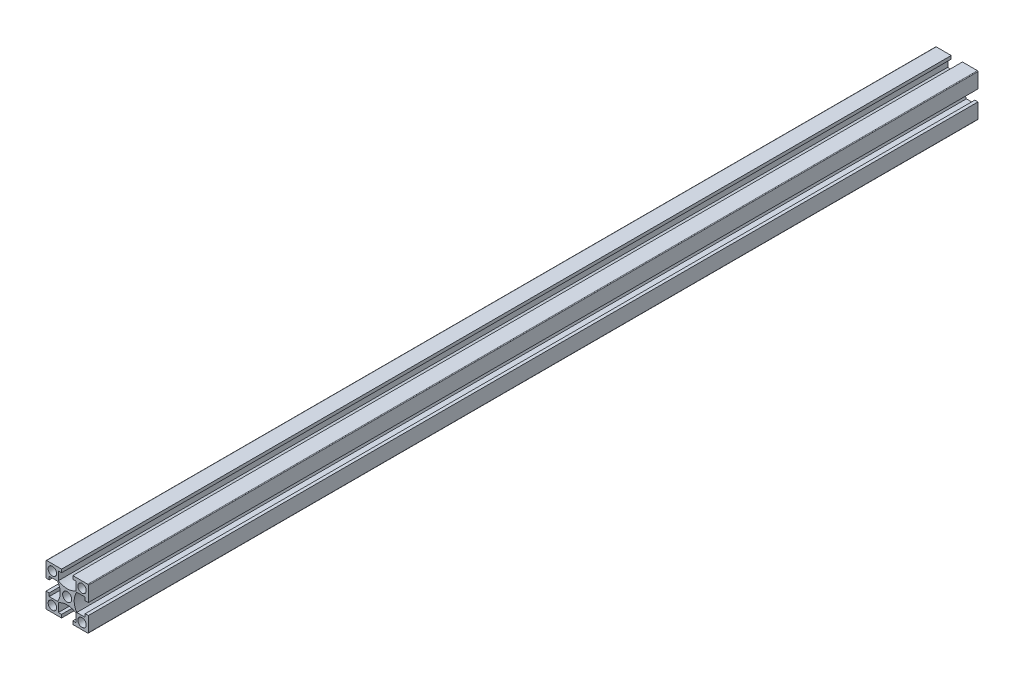
SolidWorks part; units mm, degrees
material "3.0255 (EN-AW 1350A)"
ref_plane "정면" through (0, 0, 0) normal (0, 0, 1) x (1, 0, 0)
ref_plane "윗면" through (0, 0, 0) normal (0, 1, 0) x (1, 0, 0)
ref_plane "우측면" through (0, 0, 0) normal (1, 0, 0) x (0, 0, -1)
sketch "스케치1" plane through (0, 0, 0) normal (0, 0, 1) x (1, 0, 0)
  line L0 (0, 32.0265) -> (0, -31.6588) construction
  line L1 (-10, 10) -> (-10, -10)
  line L2 (-10, 10) -> (10, 10)
  line L3 (-10, 2.65) -> (-8.5, 2.65)
  line L4 (13.6618, 0) -> (-11.6993, 0) construction
  line L5 (-8.5, 2.65) -> (-8.5, 4.15)
  line L6 (-8.5, 4.15) -> (-4.5032, 4.15)
  line L7 (-10, -2.65) -> (-8.5, -2.65)
  line L8 (-8.5, -2.65) -> (-8.5, -4.15)
  line L9 (-8.5, -4.15) -> (-4.5032, -4.15)
  line L10 (-10, -10) -> (10, -10)
  line L11 (10, 10) -> (10, -10)
  circle A0 centre (-7, 7) radius 2
  circle A1 centre (-7, -7) radius 2
  arc A2 (-4.5032, 4.15) -> (-4.5032, -4.15) centre (-11.0587, 0) cw
  circle A3 centre (0, 0) radius 2.15
  circle A4 centre (7, 7) radius 2
  circle A5 centre (7, -7) radius 2
  point P21 (-10, 0)
  point P23 (-3.3, 0)
  point P31 (0, -10)
  point P32 (0, 10)
  dimension "D3" = 4
  dimension "D9" = 6.7
  dimension "D10" = 4.3
  dimension "D11" = 7.7587
  dimension "D1" = 20
  dimension "D2" = 20
  dimension "D4" = 14
  dimension "D5" = 14
  dimension "D6" = 5.3
  dimension "D7" = 8.3
  dimension "D8" = 1.5
extrude "보스-돌출1" add sketch "스케치1" along normal blind 420 contours A0 | A4 | A3 | A5 | A1 | A2 L6 L5 L3 L1 L7 L8 L9 | L2 L11 L10 L1 region at (-6.6069, 0, 0) region at (-7, 7, 0) region at (-7, -7, 0) region at (0, 0, 0) region at (7, 7, 0) region at (7, -7, 0)
extrude "컷-돌출1" cut sketch "스케치1<3>" along normal up to next contours A2 L6 L5 L3 L1 L7 L8 L9 region at (-6.6069, 0, 0)
sketch "스케치1<3>" plane through (0, 0, 0) normal (0, 0, 1) x (1, 0, 0) same geometry as "스케치1"
pattern_circular "원형 패턴1" count 4 over 360 about axis through (0, 0, 420) along (0, 0, -1) of "컷-돌출1" reverse direction yes
fillet "필렛1" radius 0.3 4 edges at (10, -10, 210) (-10, -10, 210) (-10, 10, 210) (10, 10, 210)
sketch "스케치6" plane through (0, 10, 0) normal (0, 1, 0) x (1, 0, 0)
  line L0 (4.15, 0) -> (-4.15, 0) construction
  line L1 (-4.15, -420) -> (4.15, -420) construction
  circle A0 centre (0, -110) radius 2.5
  circle A1 centre (0, -310) radius 2.5
  dimension "D1" = 110
  dimension "D2" = 110
extrude "컷-돌출4" cut sketch "스케치6" against normal through all
sketch "스케치7" plane through (0, -10, 0) normal (0, -1, 0) x (1, 0, 0)
  line L0 (2.65, 0) -> (9.7, 0) construction
  line L1 (2.65, 420) -> (9.7, 420) construction
  circle A0 centre (0, 249.5) radius 2.5
  circle A1 centre (0, 170.5) radius 2.5
  dimension "D1" = 170.5
  dimension "D2" = 170.5
extrude "컷-돌출5" cut sketch "스케치7" against normal through all
sketch "스케치8" plane through (10, 0, 0) normal (1, 0, 0) x (0, 0, -1)
  circle A0 centre (-310, 0) radius 2.5
  circle A1 centre (-110, 0) radius 2.5
  dimension "D1" = 110
  dimension "D2" = 110
extrude "컷-돌출6" cut sketch "스케치8" against normal through all
